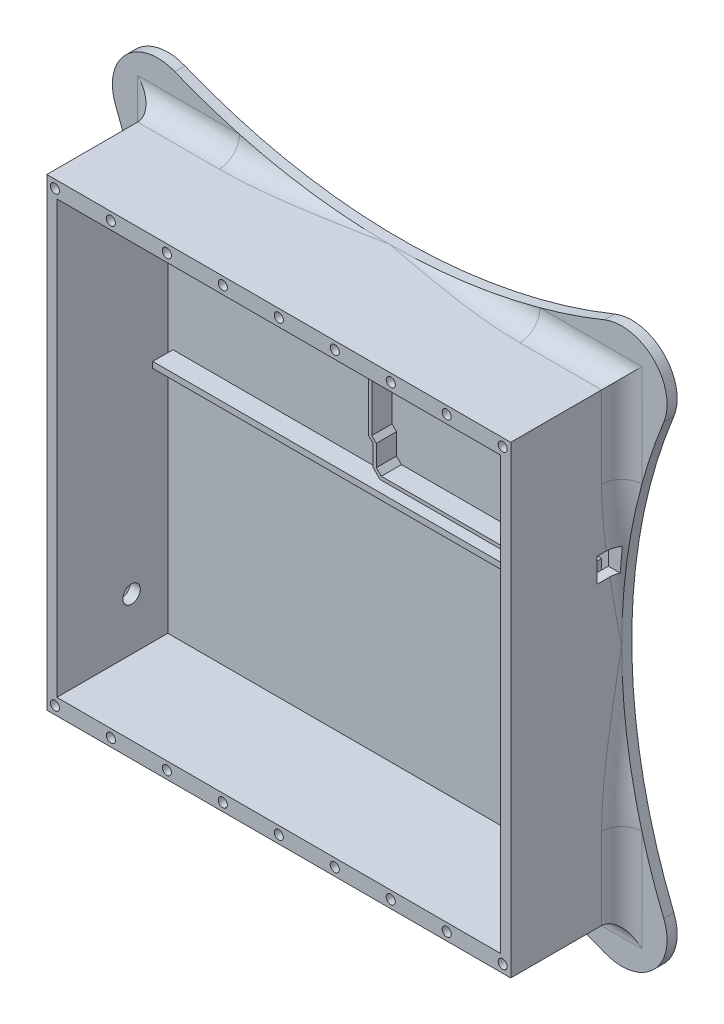
SolidWorks part; units mm, degrees
ref_plane "Front Plane" through (0, 0, 0) normal (0, 0, 1) x (1, 0, 0)
ref_plane "Top Plane" through (0, 0, 0) normal (0, 1, 0) x (1, 0, 0)
ref_plane "Right Plane" through (0, 0, 0) normal (1, 0, 0) x (0, 0, -1)
sketch "Sketch1" plane through (0, 0, 0) normal (0, 0, 1) x (1, 0, 0)
  line L0 (-115, 92.5) -> (-115, 115) construction
  line L5 (-92.5, -115) -> (92.5, -115)
  line L6 (-115, -92.5) -> (-115, 92.5)
  line L7 (-92.5, 115) -> (92.5, 115)
  line L8 (115, -92.5) -> (115, 92.5)
  line L9 (-115, -115) -> (115, 115) construction
  line L10 (-115, 115) -> (115, -115) construction
  line L11 (-115, 115) -> (-92.5, 115) construction
  line L12 (92.5, 115) -> (115, 115) construction
  line L13 (115, 92.5) -> (115, 115) construction
  line L14 (115, -115) -> (115, -92.5) construction
  line L15 (92.5, -115) -> (115, -115) construction
  line L16 (-115, -115) -> (-92.5, -115) construction
  line L17 (-115, -115) -> (-115, -92.5) construction
  line L18 (-92.5, 115) -> (-115, 115)
  line L19 (-115, 115) -> (-115, 92.5)
  line L20 (92.5, 115) -> (115, 115)
  line L21 (115, 115) -> (115, 92.5)
  line L22 (115, -92.5) -> (115, -115)
  line L23 (115, -115) -> (92.5, -115)
  line L24 (-115, -92.5) -> (-115, -115)
  line L25 (-115, -115) -> (-92.5, -115)
  arc A12 (115, 92.5) -> (92.5, 115) centre (115, 115) ccw
  arc A13 (-92.5, 115) -> (-115, 92.5) centre (-115, 115) ccw
  arc A14 (-115, -92.5) -> (-92.5, -115) centre (-115, -115) ccw
  arc A15 (92.5, -115) -> (115, -92.5) centre (115, -115) ccw
  arc A16 (-115, 92.5) -> (-99.0901, 99.0901) centre (-115, 115) ccw construction
  arc A17 (-99.0901, 99.0901) -> (-92.5, 115) centre (-115, 115) ccw construction
  arc A18 (92.5, 115) -> (99.0901, 99.0901) centre (115, 115) ccw construction
  arc A19 (99.0901, 99.0901) -> (115, 92.5) centre (115, 115) ccw construction
  arc A20 (115, -92.5) -> (99.0901, -99.0901) centre (115, -115) ccw construction
  arc A21 (99.0901, -99.0901) -> (92.5, -115) centre (115, -115) ccw construction
  arc A22 (-92.5, -115) -> (-99.0901, -99.0901) centre (-115, -115) ccw construction
  arc A23 (-99.0901, -99.0901) -> (-115, -92.5) centre (-115, -115) ccw construction
  arc A24 (-106.5203, 135.8409) -> (106.5203, 135.8409) centre (0, 397.6389) ccw
  arc A25 (135.8409, 106.5203) -> (135.8409, -106.5203) centre (397.6389, 0) ccw
  arc A26 (106.5203, -135.8409) -> (-106.5203, -135.8409) centre (0, -397.6389) ccw
  arc A27 (-135.8409, -106.5203) -> (-135.8409, 106.5203) centre (-397.6389, 0) ccw
  point P0 (0, 0)
  point P9 (-222.6923, 131.3905)
  point P21 (0, 0)
  point P32 (1.3654, 3.0913)
  point P33 (0, 0)
  point P46 (4.4567, 1.7259)
  dimension "D3" = 45
  dimension "D4" = 4
  dimension "D1" = 230
  dimension "D2" = 230
extrude "Boss-Extrude3" add sketch "Sketch1" along normal blind 5 contours L24 L25 L5 L23 L22 L8 L21 L20 L7 L18 L19 L6 | L24 A14 L25 | A14 L5 | L23 A15 L22 | A15 L5 | A15 L8 | A12 L8 | L21 A12 L20 | A12 L7 | A13 L7 | L18 A13 L19 | A13 L6 | A14 L6 region at (0, 0, 0) region at (-118.1831, -118.1831, 0) region at (-71.6551, -120.3622, 0) region at (71.6551, -120.3622, 0) region at (118.1831, -118.1831, 0) region at (-120.3622, -71.6551, 0) region at (120.3622, -71.6551, 0) region at (-120.3622, 71.6551, 0) region at (120.3622, 71.6551, 0) region at (-118.1831, 118.1831, 0) region at (118.1831, 118.1831, 0) region at (-71.6551, 120.3622, 0) region at (71.6551, 120.3622, 0)
extrude "Boss-Extrude4" add sketch "Sketch1<7>" along normal blind 60 contours L24 L25 L5 L23 L22 L8 L21 L20 L7 L18 L19 L6 region at (0, 0, 0)
sketch "Sketch1<7>" plane through (0, 0, 0) normal (0, 0, 1) x (1, 0, 0) same geometry as "Sketch1"
fillet "Fillet1" radius 10 6 edges at (115, 57.5, 5) (-57.5, -115, 5) (-115, -57.5, 5) (-57.5, 115, 5) (-115, 57.5, 5) (57.5, 115, 5)
sketch "Sketch2" plane through (0, 0, 60) normal (0, 0, 1) x (1, 0, 0)
  line L8 (-110, 110) -> (-110, -110)
  line L9 (-110, -110) -> (110, -110)
  line L10 (110, -110) -> (110, 110)
  line L11 (110, 110) -> (-110, 110)
  line L12 (-110, 110) -> (-110, -110)
  line L13 (-110, -110) -> (110, -110)
  line L14 (110, -110) -> (110, 110)
  line L15 (110, 110) -> (-110, 110)
  dimension "D1" = 5
extrude "Cut-Extrude1" cut sketch "Sketch2" against normal blind 55
sketch "Sketch3" plane through (115, 0, 0) normal (1, 0, 0) x (0, 0, -1)
  line L0 (-6.651, 44.6499) -> (-17.151, 44.6499) construction
  line L1 (-6.651, 32.6499) -> (-6.651, 44.6499) construction
  line L2 (-17.151, 44.6499) -> (-17.151, 32.6499) construction
  line L3 (-17.151, 32.6499) -> (-6.651, 32.6499) construction
  line L4 (-6.651, 44.6499) -> (-17.151, 44.6499)
  line L5 (-6.651, 32.6499) -> (-6.651, 44.6499)
  line L6 (-17.151, 44.6499) -> (-17.151, 32.6499)
  line L7 (-17.151, 32.6499) -> (-6.651, 32.6499)
extrude "Cut-Extrude2" cut sketch "Sketch3" along normal through all and the other way up to next
sketch "Sketch4" plane through (-115, 0, 0) normal (-1, 0, 0) x (0, 0, 1)
  line L0 (23, -85.3) -> (23, -77) construction
  circle A0 centre (23, -81.15) radius 4.35
  dimension "D1" = 8.7
extrude "Cut-Extrude3" cut sketch "Sketch4" against normal up to next
sketch "Sketch5" plane through (0, 0, 5) normal (0, 0, 1) x (1, 0, 0)
  line L0 (1.422, 73.6703) -> (1.422, 38.6066)
  line L1 (4.597, 76.8453) -> (1.422, 73.6703)
  line L2 (4.597, 76.8453) -> (103.022, 76.8453)
  line L3 (103.022, 76.8453) -> (103.022, 23.6323)
  line L4 (103.022, 23.6323) -> (5.9532, 23.6323)
  line L5 (5.9532, 23.6323) -> (3.6672, 25.9183)
  line L6 (3.6672, 25.9183) -> (3.6672, 36.3615)
  line L7 (3.6672, 36.3615) -> (1.422, 38.6066)
  line L8 (-0.578, 74.4987) -> (-0.578, 37.7782)
  line L9 (1.6672, 35.5331) -> (-0.578, 37.7782)
  line L10 (1.6672, 25.0898) -> (1.6672, 35.5331)
  line L11 (5.1247, 21.6323) -> (1.6672, 25.0898)
  line L12 (110, 110) -> (-110, 110)
  line L13 (-110, 110) -> (-110, -110)
  line L14 (-110, -110) -> (110, -110)
  line L15 (110, -110) -> (110, 110)
  line L16 (110, 110) -> (-110, 110)
  line L17 (-110, 110) -> (-110, -110)
  line L18 (-110, -110) -> (110, -110)
  line L19 (110, -110) -> (110, 110)
  line L20 (105.022, 21.6323) -> (5.1247, 21.6323)
  line L21 (105.022, 78.8453) -> (105.022, 44.6499)
  line L22 (3.7686, 78.8453) -> (105.022, 78.8453)
  line L23 (3.7686, 78.8453) -> (-0.578, 74.4987)
  line L24 (103.322, 77.1453) -> (103.322, 44.6499)
  line L25 (103.322, 23.3323) -> (5.8289, 23.3323)
  line L26 (5.8289, 23.3323) -> (3.3672, 25.794)
  line L27 (3.3672, 25.794) -> (3.3672, 36.2373)
  line L28 (3.3672, 36.2373) -> (1.122, 38.4824)
  line L29 (1.122, 73.7945) -> (1.122, 38.4824)
  line L30 (4.4728, 77.1453) -> (1.122, 73.7945)
  line L31 (4.4728, 77.1453) -> (103.322, 77.1453)
  line L32 (103.322, 32.6499) -> (105.022, 32.6499)
  line L33 (103.322, 44.6499) -> (105.022, 44.6499)
  line L34 (100.575, 44.6499) -> (110, 44.6499) construction
  line L36 (110, 32.6499) -> (100.575, 32.6499) construction
  line L37 (105.022, 32.6499) -> (105.022, 21.6323)
  line L38 (105.022, 78.8453) -> (105.022, 21.6323) construction
  line L39 (103.322, 32.6499) -> (103.322, 23.3323)
  line L40 (103.322, 77.1453) -> (103.322, 23.3323) construction
  dimension "D1" = 0
  dimension "D2" = 2
  dimension "D3" = 0.3
extrude "Boss-Extrude5" add sketch "Sketch5" along normal blind 10 contours L32 L39 L25 L26 L27 L28 L29 L30 L31 L24 L33 L21 L22 L23 L8 L9 L10 L11 L20 L37 region at (2.4446, 75.8227, 5)
sketch "Sketch6" plane through (0, 0, 5) normal (0, 0, 1) x (1, 0, 0)
  line L0 (-107.5, 13) -> (107.5, 13)
  line L1 (107.5, 13) -> (107.5, 16)
  line L2 (107.5, 16) -> (-107.5, 16)
  line L3 (-107.5, 16) -> (-107.5, 13)
  dimension "D1" = 3
extrude "Boss-Extrude6" add sketch "Sketch6" along normal blind 10
sketch "Sketch7" plane through (0, 0, 60) normal (0, 0, 1) x (1, 0, 0)
  line L0 (110, -110) -> (110, 110) construction
  line L1 (-115, 115) -> (110, 115)
  line L2 (-115, 115) -> (-115, 107)
  line L3 (-115, 107) -> (110, 107)
  line L4 (110, 115) -> (110, 107)
  line L6 (-115, -115) -> (110, -115)
  line L7 (-115, -115) -> (-115, -107)
  line L8 (-115, -107) -> (110, -107)
  line L9 (110, -115) -> (110, -107)
  dimension "D1" = 8
  dimension "D2" = 8
extrude "Boss-Extrude7" add sketch "Sketch7" against normal up to surface (55 mm away) up to face at (43.1864, 45.1859, 5)
sketch "Sketch8" plane through (0, 0, 60) normal (0, 0, 1) x (1, 0, 0)
  line L0 (-115, -115) -> (115, -115) construction
  circle A0 centre (-111, -111) radius 2.25
  circle A1 centre (-83.25, -111) radius 2.25
  circle A2 centre (-55.5, -111) radius 2.25
  circle A3 centre (-27.75, -111) radius 2.25
  circle A4 centre (0, -111) radius 2.25
  circle A5 centre (27.75, -111) radius 2.25
  circle A6 centre (55.5, -111) radius 2.25
  circle A7 centre (83.25, -111) radius 2.25
  circle A8 centre (111, -111) radius 2.25
  circle A9 centre (-111, 111) radius 2.25
  circle A10 centre (-83.25, 111.0161) radius 2.25
  circle A11 centre (-55.5, 111.0321) radius 2.25
  circle A12 centre (-27.75, 111.0482) radius 2.25
  circle A13 centre (0, 111.0642) radius 2.25
  circle A14 centre (27.75, 111.0803) radius 2.25
  circle A15 centre (55.5, 111.0963) radius 2.25
  circle A16 centre (83.25, 111.1124) radius 2.25
  circle A17 centre (111, 111.1284) radius 2.25
  dimension "D1" = 4.5
  dimension "D2" = 4
  dimension "D5" = 4.5
  dimension "D3" = 4
  dimension "D4" = 4
  dimension "D6" = 4
  dimension "D7" = 4
  dimension "D8" = 4
extrude "Cut-Extrude4" cut sketch "Sketch8" against normal blind 20
